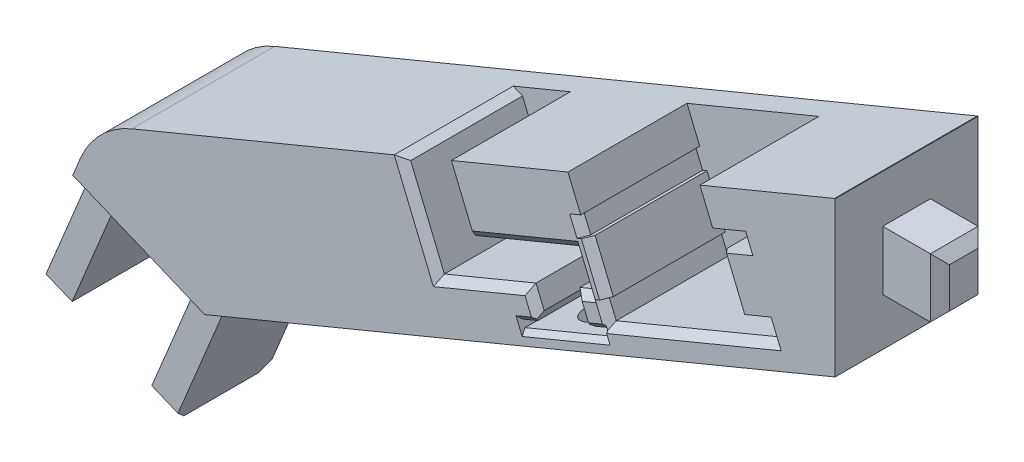
SolidWorks part; units mm, degrees
ref_plane "Front Plane" through (0, 0, 0) normal (0, 0, 1) x (1, 0, 0)
ref_plane "Top Plane" through (0, 0, 0) normal (0, 1, 0) x (1, 0, 0)
ref_plane "Right Plane" through (0, 0, 0) normal (1, 0, 0) x (0, 0, -1)
sketch "Sketch1" plane through (0, 0, 0) normal (0, 0, 1) x (1, 0, 0)
  line L7 (0, 216.4784) -> (-153.0734, 153.0734)
  line L8 (-153.0734, 153.0734) -> (-216.4784, 0)
  line L10 (0, 248.9502) -> (-176.0344, 176.0344)
  line L11 (-176.0344, 176.0344) -> (-244.1948, 11.4805)
  line L12 (0, 248.9502) -> (0, 216.4784)
  line L14 (-244.1948, 11.4805) -> (-244.1948, 0)
  line L15 (-244.1948, 0) -> (-216.4784, 0)
  line L18 (0, 0) -> (-212.4923, 88.0172) construction
  line L20 (0, 0) -> (-88.0172, 212.4923) construction
  line L27 (0, 248.9502) -> (-176.0344, 176.0344) construction
  line L28 (0, 216.4784) -> (-153.0734, 153.0734) construction
  line L29 (153.0734, 153.0734) -> (0, 216.4784) construction
  line L30 (176.0344, 176.0344) -> (0, 248.9502) construction
  line L31 (153.0734, 153.0734) -> (76.5367, 184.7759) [skipped]
  line L32 (216.4784, 0) -> (153.0734, 153.0734) construction
  line L33 (244.1948, 11.4805) -> (176.0344, 176.0344) construction
  line L34 (216.4784, 0) -> (184.7759, 76.5367) [skipped]
  line L35 (153.0734, -153.0734) -> (184.7759, -76.5367) [skipped]
  line L36 (0, -216.4784) -> (76.5367, -184.7759) [skipped]
  line L37 (-153.0734, -153.0734) -> (-76.5367, -184.7759) [skipped]
  line L38 (-216.4784, 0) -> (-184.7759, -76.5367) [skipped]
  dimension "D3" = 30
  dimension "D2" = 30
extrude "Boss-Extrude1" add sketch "Sketch1" along normal blind 30
sketch "Sketch3" plane through (0, 0, 30) normal (0, 0, 1) x (1, 0, 0)
  line L0 (-176.0344, 176.0344) -> (-153.0734, 153.0734) construction
  line L1 (0, 232.7143) -> (-164.5539, 164.5539) construction
  line L2 (0, 216.4784) -> (0, 248.9502) construction
  line L3 (-244.1948, 11.4805) -> (-216.4784, 0) construction
  line L4 (-164.5539, 164.5539) -> (-230.3366, 5.7403) construction
  line L5 (-82.2769, 198.6341) -> (-76.5367, 184.7759) construction
  line L6 (-153.0734, 153.0734) -> (0, 216.4784) construction
  line L7 (-186.6893, 71.9173) -> (-182.8625, 81.1561)
  line L8 (-184.7759, 76.5367) -> (-198.6341, 82.2769) construction
  line L9 (-216.4784, 0) -> (-153.0734, 153.0734) construction
  line L10 (-182.8625, 81.1561) -> (-192.1013, 84.9829)
  line L12 (-195.9281, 75.7441) -> (-186.6893, 71.9173)
  line L13 (-81.1561, 182.8625) -> (-71.9173, 186.6893)
  line L14 (-71.9173, 186.6893) -> (-75.7441, 195.9281)
  line L16 (-84.9829, 192.1013) -> (-81.1561, 182.8625)
  line L17 (-75.7441, 195.9281) -> (-72.8154, 197.1412)
  line L18 (-72.8154, 197.1412) -> (-75.4942, 203.6084)
  line L19 (-75.4942, 203.6084) -> (-97.6673, 194.424)
  line L20 (-106.9061, 190.5971) -> (-104.2273, 184.13)
  line L21 (-104.2273, 184.13) -> (-84.9829, 192.1013)
  line L22 (-106.9061, 190.5971) -> (-111.881, 202.6076)
  line L23 (0, 248.9502) -> (-176.0344, 176.0344) construction
  line L24 (-97.6673, 194.424) -> (-102.6422, 206.4344)
  line L25 (-102.6422, 206.4344) -> (-111.881, 202.6076)
  line L26 (-192.1013, 84.9829) -> (-184.13, 104.2273)
  line L27 (-184.13, 104.2273) -> (-202.6076, 111.881)
  line L28 (-176.0344, 176.0344) -> (-244.1948, 11.4805) construction
  line L29 (-202.6076, 111.881) -> (-206.4344, 102.6422)
  line L30 (-206.4344, 102.6422) -> (-194.424, 97.6673)
  line L31 (-194.424, 97.6673) -> (-203.6084, 75.4942)
  line L32 (-203.6084, 75.4942) -> (-197.1412, 72.8154)
  line L33 (-197.1412, 72.8154) -> (-195.9281, 75.7441)
  point P24 (-184.7759, 76.5367)
  dimension "D1" = 5
  dimension "D2" = 5
  dimension "D3" = 10
  dimension "D4" = 5
  dimension "D5" = 5
  dimension "D6" = 10
  dimension "D7" = 3.17
  dimension "D8" = 7
  dimension "D9" = 34
  dimension "D10" = 10
  dimension "D11" = 3.17
  dimension "D12" = 34
  dimension "D13" = 7
  dimension "D14" = 10
  dimension "D15" = 10
  dimension "D16" = 10
sketch "Sketch4" plane through (-244.1948, 0, 0) normal (-1, 0, 0) x (0, 0, 1)
  line L1 (0, 0) -> (30, 0)
  line L2 (0, 0) -> (0, 11.4805)
  line L3 (0, 11.4805) -> (30, 11.4805)
  line L4 (30, 0) -> (30, 11.4805)
extrude "Boss-Extrude2" add sketch "Sketch4" along normal blind 50
sketch "Sketch5" plane through (0, 11.4805, 0) normal (0, 1, 0) x (1, 0, 0)
  line L0 (-244.1948, -15) -> (-294.1948, -15) construction
  line L1 (-244.1948, -30) -> (-244.1948, 0) construction
  line L2 (-294.1948, -30) -> (-294.1948, 0) construction
  line L3 (-269.1948, -15) -> (-269.1948, 0) construction
  line L4 (-294.1948, 0) -> (-244.1948, 0) construction
  line L5 (-281.6948, -7.5) -> (-294.1948, -7.5) construction
  line L6 (-281.6948, -7.5) -> (-281.6948, -30) construction
  line L7 (-294.1948, -30) -> (-244.1948, -30) construction
  line L8 (-256.6948, -7.5) -> (-244.1948, -7.5) construction
  line L9 (-256.6948, -7.5) -> (-256.6948, -30) construction
  line L12 (-281.6948, -6) -> (-256.6948, -6)
  line L13 (-281.6948, -24) -> (-256.6948, -24)
  arc A2 (-256.6948, -24) -> (-256.6948, -6) centre (-256.6948, -15) ccw
  arc A3 (-281.6948, -6) -> (-281.6948, -24) centre (-281.6948, -15) ccw
extrude "Cut-Extrude1" cut sketch "Sketch5" against normal blind 5
sketch "Sketch7" plane through (0, 6.4805, 0) normal (0, 1, 0) x (1, 0, 0)
  line L0 (-256.6948, -11.5) -> (-281.6948, -11.5)
  line L1 (-256.6948, -6) -> (-256.6948, -24) construction
  line L2 (-256.6948, -18.5) -> (-281.6948, -18.5)
  arc A1 (-256.6948, -24) -> (-256.6948, -6) centre (-256.6948, -15) ccw construction
  arc A2 (-256.6948, -18.5) -> (-256.6948, -11.5) centre (-256.6948, -15) ccw
  arc A3 (-281.6948, -11.5) -> (-281.6948, -18.5) centre (-281.6948, -15) ccw
  dimension "D1" = 7
extrude "Cut-Extrude3" cut sketch "Sketch7" against normal up to surface (6.4805 mm away) up to face at (-255.3366, 0, 15)
fillet "Fillet1" radius 10 2 edges at (-294.1948, 5.7403, 0) (-294.1948, 5.7403, 30)
chamfer "Chamfer3" distance 22.5 angle 22.5 1 edges at (0, 248.9502, 15) first distance on face at (-88.0172, 212.4923, 15)
chamfer "Chamfer1" distance 15 angle 54 1 edges at (0, 228.4091, 0) first distance on face at (0, 228.4091, 15)
chamfer "Chamfer2" distance 15 angle 54 1 edges at (0, 228.4091, 30) first distance on face at (0, 228.4091, 22.5)
extrude "Cut-Extrude4" cut sketch "Sketch3" against normal blind 25
sketch "Sketch8" plane through (0, 0, 30) normal (0, 0, 1) x (1, 0, 0)
  line L0 (-20.6457, 224.1333) -> (-173.822, 160.6856) construction
  line L1 (-20.6457, 207.9267) -> (-20.6457, 240.3398) construction
  line L2 (-68.1304, 193.6699) -> (-69.6611, 197.3654)
  line L3 (-75.0187, 210.2997) -> (-74.0948, 210.6824)
  line L5 (-76.7736, 217.1495) -> (-49.0572, 228.6301)
  line L6 (-40.8351, 224.459) -> (-39.3044, 220.7635)
  line L8 (-68.1304, 193.6699) -> (-33.9468, 207.8292)
  line L9 (-72.8154, 197.1412) -> (-75.4942, 203.6084) construction
  line L10 (-71.9173, 186.6893) -> (-20.6457, 207.9267) construction
  line L11 (-69.6611, 197.3654) -> (-68.7372, 197.7481)
  line L12 (-68.7372, 197.7481) -> (-72.5641, 206.9869)
  line L13 (-72.5641, 206.9869) -> (-73.4879, 206.6042)
  line L14 (-35.4776, 211.5247) -> (-41.0208, 209.2286)
  line L15 (-41.0208, 209.2286) -> (-44.8477, 218.4674)
  line L16 (-44.8477, 218.4674) -> (-39.3044, 220.7635)
  line L17 (-35.4776, 211.5247) -> (-33.9468, 207.8292)
  line L18 (-73.4879, 206.6042) -> (-75.0187, 210.2997)
  line L19 (-40.8351, 224.459) -> (-46.3784, 222.1629)
  line L20 (-46.3784, 222.1629) -> (-49.0572, 228.6301)
  line L21 (-74.0948, 210.6824) -> (-76.7736, 217.1495)
  dimension "D1" = 37
  dimension "D2" = 3
  dimension "D3" = 5
  dimension "D4" = 4
  dimension "D5" = 10
  dimension "D6" = 1
  dimension "D7" = 4
  dimension "D8" = 10
  dimension "D9" = 6
  dimension "D10" = 6
  dimension "D11" = 4
  dimension "D12" = 4
  dimension "D13" = 1
extrude "Cut-Extrude5" cut sketch "Sketch8" against normal blind 25
sketch "Sketch9" plane through (0, 240.3398, 0) normal (0, 1, 0) x (1, 0, 0)
  line L1 (-20.6457, -30) -> (0, -30)
  line L2 (-20.6457, -30) -> (-20.6457, 0)
  line L3 (-20.6457, 0) -> (0, 0)
  line L4 (0, -30) -> (0, 0)
extrude "Cut-Extrude6" cut sketch "Sketch9" against normal blind 40 body kept at (-20.7873, 240.3398, 30)
sketch "Sketch10" plane through (-20.6457, 0, 0) normal (1, 0, 0) x (0, 0, -1)
  line L8 (-10, 217.9267) -> (-10, 230.3398)
  line L9 (-10, 230.3398) -> (-20, 230.3398)
  line L10 (-20, 230.3398) -> (-20, 217.9267)
  line L11 (-20, 217.9267) -> (-10, 217.9267)
  line L12 (-10, 217.9267) -> (-10, 230.3398)
  line L13 (-10, 230.3398) -> (-20, 230.3398)
  line L14 (-20, 230.3398) -> (-20, 217.9267)
  line L15 (-20, 217.9267) -> (-10, 217.9267)
  dimension "D1" = 10
extrude "Boss-Extrude3" add sketch "Sketch10" along normal blind 12
sketch "Sketch11" plane through (-76.5367, 184.7759, 0) normal (0.3827, -0.9239, 0) x (0.9239, 0.3827, 0)
  line L0 (-10, 4.5) -> (10, 4.5)
  line L2 (-10, 30) -> (-10, 4.5)
  line L4 (10, 30) -> (10, 4.5)
  line L6 (-5, 5) -> (-5, 30) construction
  line L7 (5, 5) -> (5, 30) construction
  line L8 (10, 30) -> (-10, 30)
  line L9 (5, 30) -> (60.4959, 30) construction
  dimension "D1" = 5
  dimension "D2" = 5
  dimension "D5" = 0
extrude "Cut-Extrude7" cut sketch "Sketch11" against normal blind 4
sketch "Sketch12" plane through (-184.7759, 76.5367, 0) normal (0.9239, -0.3827, 0) x (0, 0, -1)
  line L0 (-30, -82.8427) -> (-30, -5) construction
  line L1 (-30, -15) -> (0, -15)
  line L2 (-30, -15) -> (-30, 16)
  line L3 (-30, 16) -> (0, 16)
  line L4 (0, -15) -> (0, 16)
  line L5 (0, -82.8427) -> (0, 82.8427) construction
  line L6 (-5, -5) -> (-30, -5) construction
  line L7 (-5, 5) -> (-30, 5) construction
  dimension "D1" = 10
  dimension "D2" = 11
extrude "Cut-Extrude8" cut sketch "Sketch12" against normal blind 2
chamfer "Chamfer4" distance 1.5 angle 45 30 edges at (-42.9343, 213.848, 30) (-74.2533, 208.452, 30) (-40.0698, 222.6112, 30) (-68.8957, 195.5176, 30) (-34.7122, 209.6769, 30) (-51.0386, 200.7495, 30) (-82.6868, 186.558, 17.5) (-108.0542, 193.3688, 30) (-83.8349, 189.3296, 30) (-94.6051, 188.1156, 30) (-73.448, 190.3848, 17.5) (-100.1548, 200.4292, 30) (-74.5961, 193.1565, 30) (-74.2798, 196.5347, 30) (-74.1548, 200.3748, 30) (-86.5808, 199.0162, 30) (-188.5371, 72.6827, 17.5) (-192.2326, 74.2134, 30) (-196.5347, 74.2798, 30) (-200.3748, 74.1548, 30) (-199.0162, 86.5808, 30) (-200.4292, 100.1548, 30) (-184.7102, 81.9215, 17.5) (-188.4058, 83.4522, 30) (-188.1156, 94.6051, 30) (-193.3688, 108.0542, 30) (-111.881, 202.6076, 17.5) (-102.6422, 206.4344, 17.5) (-206.4344, 102.6422, 17.5) (-202.6076, 111.881, 17.5)
sketch "Sketch13" plane through (0, 0, 0) normal (0, 0, -1) x (-1, 0, 0)
  line L0 (157.1443, 143.2452) -> (184.8607, 154.7257) construction
  line L1 (178.653, 91.3188) -> (153.0734, 153.0734) construction
  line L2 (176.0344, 176.0344) -> (244.1948, 11.4805) construction
  line L3 (153.0734, 153.0734) -> (180.7898, 164.5539) construction
  line L4 (153.0734, 153.0734) -> (216.4784, 0)
  line L5 (216.4784, 0) -> (308.5556, 0)
  line L6 (308.5556, 0) -> (180.7898, 164.5539)
  line L7 (180.7898, 164.5539) -> (153.0734, 153.0734)
extrude "Cut-Extrude9" cut sketch "Sketch13" against normal blind 30
sketch "Sketch14" plane through (31.7025, 76.5367, 0) normal (-0.3827, -0.9239, 0) x (0.9239, -0.3827, 0)
  line L0 (-230, 30) -> (-230, 0) construction
  line L1 (-230, 5.1) -> (-224.05, 5.1)
  line L2 (-230, 5.1) -> (-230, 24.9)
  line L3 (-230, 24.9) -> (-224.05, 24.9)
  line L4 (-224.05, 5.1) -> (-224.05, 24.9)
  line L5 (-200, 30) -> (-200, 0) construction
  line L6 (-200, 5.1) -> (-205.95, 5.1)
  line L7 (-200, 5.1) -> (-200, 24.9)
  line L8 (-200, 24.9) -> (-205.95, 24.9)
  line L9 (-205.95, 5.1) -> (-205.95, 24.9)
  line L10 (-230, 0) -> (-200, 0) construction
  line L11 (-230, 30) -> (-200, 30) construction
  dimension "D1" = 5.1
  dimension "D2" = 5.1
  dimension "D3" = 5.95
extrude "Boss-Extrude4" add sketch "Sketch14" along normal blind 30
fillet "Fillet2" radius 20 1 edges at (-176.0344, 176.0344, 15)
chamfer "Chamfer5" distance 2 angle 45 10 edges at (-8.6457, 230.3398, 15) (-8.6457, 224.1333, 20) (-8.6457, 217.9267, 15) (-8.6457, 224.1333, 10) (-167.3024, 126.4955, 5.1) (-170.051, 127.634, 15) (-167.3024, 126.4955, 24.9) (-189.5217, 135.699, 24.9) (-189.5217, 135.699, 5.1) (-186.7732, 134.5605, 15)
chamfer "Chamfer6" distance 1.5 angle 45 1 edges at (-70.6506, 202.3675, 30)
sketch "Sketch15" plane through (0, 0, 4.5) normal (0, 0, 1) x (1, 0, 0)
  line L0 (-85.7755, 180.9491) -> (-86.7705, 183.3512)
  line L1 (-87.3062, 184.6446) -> (-85.7755, 180.9491) construction
  line L2 (-86.7705, 183.3512) -> (-82.1511, 185.2646)
  line L3 (-68.8286, 192.2983) -> (-67.2979, 188.6027) construction
  line L4 (-68.2929, 191.0048) -> (-67.2979, 188.6027)
  line L5 (-67.2979, 188.6027) -> (-71.9173, 186.6893)
  line L6 (-87.3062, 184.6446) -> (-68.8286, 192.2983) construction
  line L7 (-82.1511, 185.2646) -> (-81.1561, 182.8625)
  line L8 (-72.9123, 189.0914) -> (-71.9173, 186.6893)
  line L9 (-68.6373, 191.8363) -> (-67.2979, 188.6027) construction
  line L10 (-81.1561, 182.8625) -> (-85.7755, 180.9491)
  line L11 (-72.9123, 189.0914) -> (-68.2929, 191.0048)
  dimension "D1" = 1.4
  dimension "D2" = 5
  dimension "D3" = 5
extrude "Boss-Extrude5" add sketch "Sketch15" along normal up to surface (25.5 mm away) up to face at (-124.378, 179.2212, 30)
sketch "Sketch16" plane through (-4.6194, -1.9134, 0) normal (0.9239, 0.3827, 0) x (0, 0, -1)
  line L0 (-30, 200) -> (-4.5, 200) construction
  line L1 (-30, 202.6) -> (-25.4, 202.6)
  line L2 (-30, 202.6) -> (-30, 200)
  line L3 (-30, 200) -> (-25.4, 200)
  line L4 (-25.4, 202.6) -> (-25.4, 200)
  dimension "D1" = 4.6
extrude "Boss-Extrude6" add sketch "Sketch16" along normal blind 10
chamfer "Chamfer7" distance 1 angle 45 3 edges at (-70.5979, 191.5654, 30) (-85.6894, 185.3143, 30) (-77.5317, 187.178, 30)
fillet "Fillet3" radius 5 4 edges at (-72.4148, 187.8904, 4.5) (-81.6536, 184.0635, 4.5) (-72.4148, 187.8904, 25.4) (-81.6536, 184.0635, 25.4)
